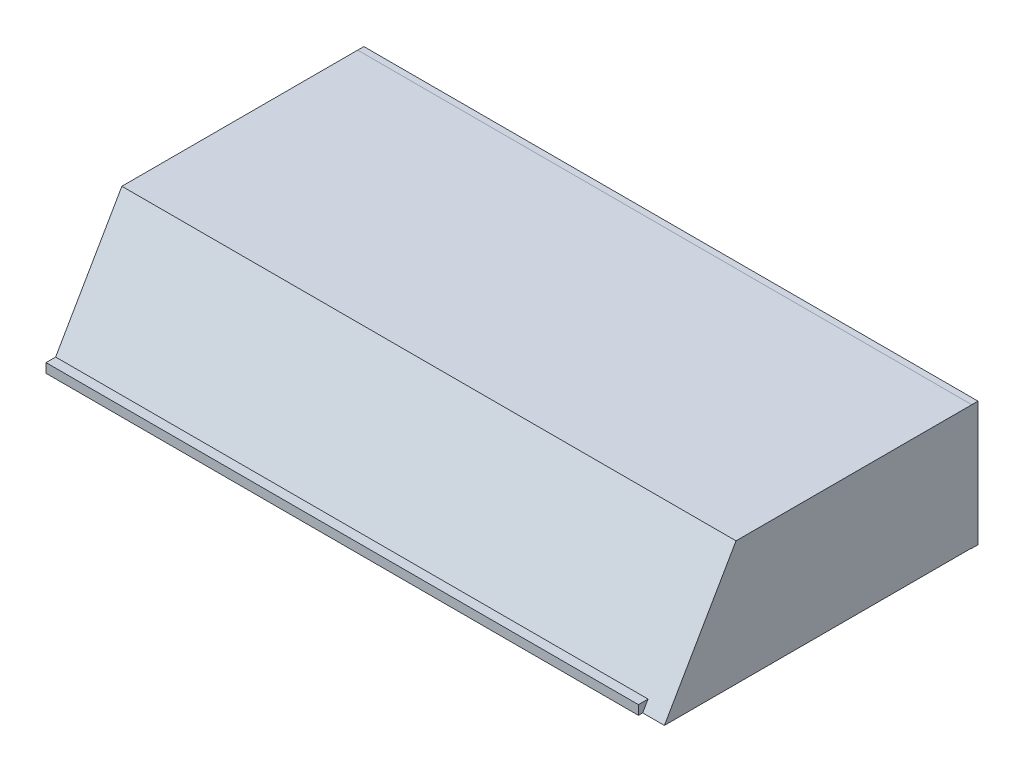
SolidWorks part; units mm, degrees
ref_plane "Alzado" through (0, 0, 0) normal (0, 0, 1) x (1, 0, 0)
ref_plane "Planta" through (0, 0, 0) normal (0, 1, 0) x (1, 0, 0)
ref_plane "Vista lateral" through (0, 0, 0) normal (1, 0, 0) x (0, 0, -1)
sketch "Sketch1" plane through (0, 0, 0) normal (1, 0, 0) x (0, 0, -1)
  line L0 (22.1085, 0) -> (32.4418, 17.8992)
  line L3 (-73.8644, -51.971) -> (121.1356, -51.9647) construction
  line L4 (22.1085, 0) -> (121.18, 0)
  line L5 (121.18, 0) -> (121.2142, 40)
  line L6 (45.2007, 40) -> (121.2142, 40)
  line L7 (32.4418, 17.8992) -> (45.2007, 40)
  line L8 (121.1416, -44.9647) -> (121.18, 0) construction
  dimension "D1" = 120
  dimension "D2" = 40
  dimension "D3" = 120
  dimension "D4" = 76.0135
extrude "Boss-Extrude1" add sketch "Sketch1" along normal blind 198
shell "Shell1" thickness 7 removed face at (99, 0, -71.6442)
sketch "Sketch2" plane through (0, 0, 0) normal (-1, 0, 0) x (0, 0, 1)
  line L0 (-30.1912, 0) -> (-32.9749, 0)
  line L1 (-32.9749, 0) -> (-52.026, 33)
  line L2 (73.8644, -51.971) -> (-121.1356, -51.9647) construction
  line L3 (-52.026, 33) -> (-49.2423, 33)
  line L4 (-49.2423, 33) -> (-30.1912, 0)
  dimension "D1" = 120
extrude "Boss-Extrude2" add sketch "Sketch2" against normal blind 191
sketch "Sketch3" plane through (0, 0, 0) normal (-1, 0, 0) x (0, 0, 1)
  line L0 (-45.2007, 40) -> (-22.1085, 0) construction
  line L1 (-121.18, 0) -> (-20.7382, 0)
  line L2 (-121.18, 0) -> (-115.9838, 3)
  line L3 (-115.9838, 3) -> (-20.7382, 3)
  line L4 (-20.7382, 0) -> (-20.7382, 3)
  line L5 (-121.2142, 40) -> (-45.2007, 40) construction
  dimension "D1" = 95.2456
  dimension "D2" = 6
  dimension "D3" = 150.002
  dimension "D4" = 37
extrude "Boss-Extrude3" add sketch "Sketch3" against normal blind 191
sketch "Sketch4" plane through (0, 3, 0) normal (0, 1, 0) x (1, 0, 0)
  line L0 (191, 114.1826) -> (7, 114.1826) construction
  line L1 (7, 114.1826) -> (7, 34.7068) construction
  circle A0 centre (11, 109.1826) radius 1.585
  circle A1 centre (12.0103, 44.0696) radius 1.585
  dimension "D1" = 3.17
  dimension "D4" = 3.17
  dimension "D2" = 5
  dimension "D3" = 4
extrude "Cut-Extrude1" cut sketch "Sketch4" against normal blind 5
ref_plane "Plane1" through (99, 0, 0) normal (1, 0, 0) x (0, 0, -1)
mirror "Mirror1" about plane through (99, 0, 0) normal (1, 0, 0) of "Cut-Extrude1"
sketch "Sketch5" plane through (0, 3, 0) normal (0, 1, 0) x (1, 0, 0)
  line L0 (191, 34.7068) -> (191, 114.1826) construction
  line L1 (187.2466, 56.4996) -> (77.2466, 56.4734)
  line L2 (187.2466, 56.4996) -> (187.2609, 91.4996)
  line L3 (187.2609, 91.4996) -> (77.2609, 91.4734)
  line L4 (77.2466, 56.4734) -> (77.2609, 91.4734)
  line L5 (191, 114.1826) -> (7, 114.1826) construction
  dimension "D1" = 35
  dimension "D2" = 110
  dimension "D3" = 110
  dimension "D4" = 35
  dimension "D5" = 179.976
  dimension "D6" = 0.014
sketch "Sketch6" plane through (0, -0.1036, -121.1799) normal (0, -0.0009, -1) x (-1, 0, 0)
  line L1 (-198, 40.1036) -> (0, 40.1036)
  line L2 (-198, 40.1036) -> (-198, 0)
  line L3 (-198, 0) -> (0, 0)
  line L4 (0, 40.1036) -> (0, 0)
extrude "Boss-Extrude4" add sketch "Sketch6" along normal blind 2
